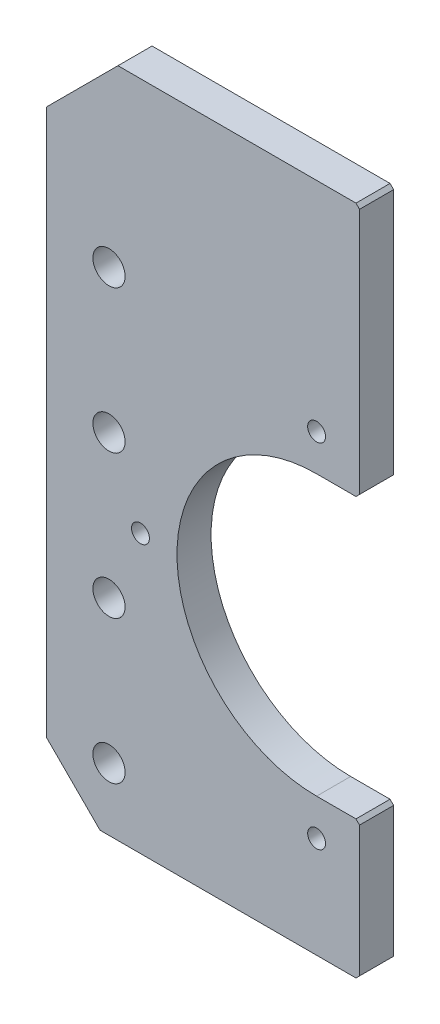
SolidWorks part; units mm, degrees
material "6061-T6 (SS)"
ref_plane "Front Plane" through (0, 0, 0) normal (0, 0, 1) x (1, 0, 0)
ref_plane "Top Plane" through (0, 0, 0) normal (0, 1, 0) x (1, 0, 0)
ref_plane "Right Plane" through (0, 0, 0) normal (1, 0, 0) x (0, 0, -1)
sketch "Sketch1" plane through (0, 0, 0) normal (0, 0, 1) x (1, 0, 0)
  line L0 (0, -39) -> (12, -39)
  line L1 (12, -39) -> (12, -77.5)
  line L2 (12, -77.5) -> (-60.5, -77.5)
  line L3 (-75.5, -62.5) -> (-75.5, 90)
  line L4 (-75.5, 90) -> (-55.5, 110)
  line L5 (-55.5, 110) -> (12, 110)
  line L6 (12, 110) -> (12, 39)
  line L7 (12, 39) -> (0, 39)
  line L8 (-38, 8.8681) -> (-38, 0) construction
  line L9 (-28, 15.1907) -> (-28, 3.6129) construction
  line L10 (-58, 60) -> (-58, 20) construction
  line L11 (-58, 20) -> (-58, -20) construction
  line L12 (-58, -20) -> (-58, -60) construction
  line L13 (55, 0) -> (-55, 0) construction
  line L14 (-75.5, -62.5) -> (-60.5, -77.5)
  arc A0 (0, 39) -> (0, -39) centre (0, 0) ccw
  circle A1 centre (0, 0) radius 49.2125 construction
  point P19 (0, 49.2125)
  point P20 (-49.2125, 0)
  point P21 (0, -49.2125)
  point P22 (-58, 0)
  dimension "D12" = 98.425
  dimension "D1" = 10
  dimension "D2" = 28
  dimension "D3" = 17.5
  dimension "D4" = 40
  dimension "D5" = 20
  dimension "D6" = 17.5
  dimension "D7" = 110
  dimension "D8" = 78
  dimension "D9" = 45
  dimension "D10" = 50
  dimension "D11" = 90
  dimension "D13" = 45
  dimension "D14" = 15
extrude "Boss-Extrude1" add sketch "Sketch1" along normal mid plane 9.525
hole_wizard "M8 Clearance Hole1" positions "Sketch2" profile "Sketch3" hole size "M8" standard "ANSI Metric" end condition up to next
sketch "Sketch2" plane through (0, 0, 4.7625) normal (0, 0, 1) x (1, 0, 0)
  point P0 (-58, 60)
  point P3 (-58, 20)
  point P6 (-58, -20)
  point P9 (-58, -60)
sketch "Sketch3" plane through (-58, 60, 4.7625) normal (1, 0, 0) x (0, -1, 0)
  line L0 (0, 0) -> (0, 9.525)
  line L1 (0, 9.525) -> (4.5, 9.525)
  line L2 (4.5, 9.525) -> (4.5, 0)
  line L5 (4.5, 0) -> (0, 0)
  line L11 (0, -6.35) -> (0, 107.95) construction
  dimension "Thru Hole Dia." = 9
  dimension "Thru Hole Depth" = 9.525
hole_wizard "M6x1.0 Tapped Hole1" positions "Sketch4" profile "Sketch5" tap size "M6x1.0" standard "ANSI Metric" end condition up to next
sketch "Sketch4" plane through (0, 0, 4.7625) normal (0, 0, 1) x (1, 0, 0)
  point P0 (0, 49.2125)
  point P3 (-49.2125, 0)
  point P6 (0, -49.2125)
sketch "Sketch5" plane through (0, 49.2125, 4.7625) normal (1, 0, 0) x (0, -1, 0)
  line L0 (0, 0) -> (0, 9.525)
  line L1 (0, 9.525) -> (2.5, 9.525)
  line L2 (2.5, 9.525) -> (2.5, 0)
  line L5 (2.5, 0) -> (0, 0)
  line L11 (0, -6.35) -> (0, 107.95) construction
  dimension "Thru Tap Drill Dia." = 5
  dimension "Thru Tap Drill Depth" = 9.525
cosmetic thread "Hole Thread1" parameters "D2"=6
cosmetic thread "Hole Thread2" parameters "D2"=6
cosmetic thread "Hole Thread3" parameters "D2"=6
chamfer "Chamfer1" distance 1 4 edges at (12, -77.5, 0) (12, -39, 0) (12, 39, 0) (12, 110, 0)
